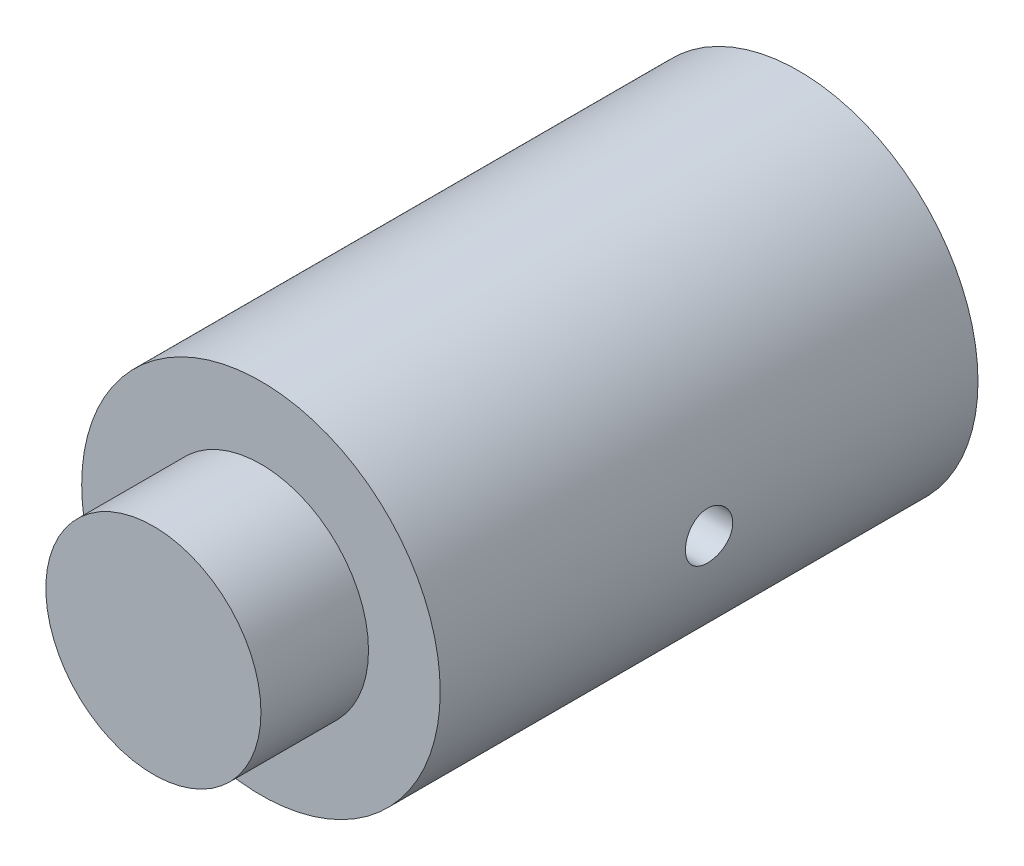
SolidWorks part; units mm, degrees
ref_plane "Front Plane" through (0, 0, 0) normal (0, 0, 1) x (1, 0, 0)
ref_plane "Top Plane" through (0, 0, 0) normal (0, 1, 0) x (1, 0, 0)
ref_plane "Right Plane" through (0, 0, 0) normal (1, 0, 0) x (0, 0, -1)
sketch "Sketch1" plane through (0, 0, 0) normal (0, 0, 1) x (1, 0, 0)
  circle A0 centre (0, 0) radius 25
  dimension "D1" = 50
extrude "Boss-Extrude1" add sketch "Sketch1" along normal blind 75 contours A0
sketch "Sketch2" plane through (0, 0, 75) normal (0, 0, 1) x (1, 0, 0)
  circle A0 centre (0, 0) radius 15
  dimension "D1" = 30
extrude "Boss-Extrude2" add sketch "Sketch2" along normal blind 15
sketch "Sketch3" plane through (0, 0, 0) normal (1, 0, 0) x (0, 0, -1)
  line L0 (-75, 0) -> (0, 0) construction
  line L1 (-75, 25) -> (-75, -25) construction
  circle A0 centre (-37.5, 0) radius 3.3
  dimension "D1" = 6.6
extrude "Cut-Extrude1" cut sketch "Sketch3" against normal blind 50 and the other way blind 50 contours A0
ref_plane "Plane1" through (0, 0, 0) normal (0, 0.7071, -0.7071) x (-1, 0, 0)
ref_axis "Axis1" through (25, 0, 37.5) along (-1, 0, 0)
sketch "Sketch4" plane through (0, 0, 0) normal (0, 0.7071, -0.7071) x (-1, 0, 0)
  line L0 (-25, 26.5165) -> (25, 26.5165) construction
  circle A0 centre (0, 26.5165) radius 4.8549
ref_plane "Plane2" through (0, -18.75, 18.75) normal (0, 0.7071, -0.7071) x (-1, 0, 0)
